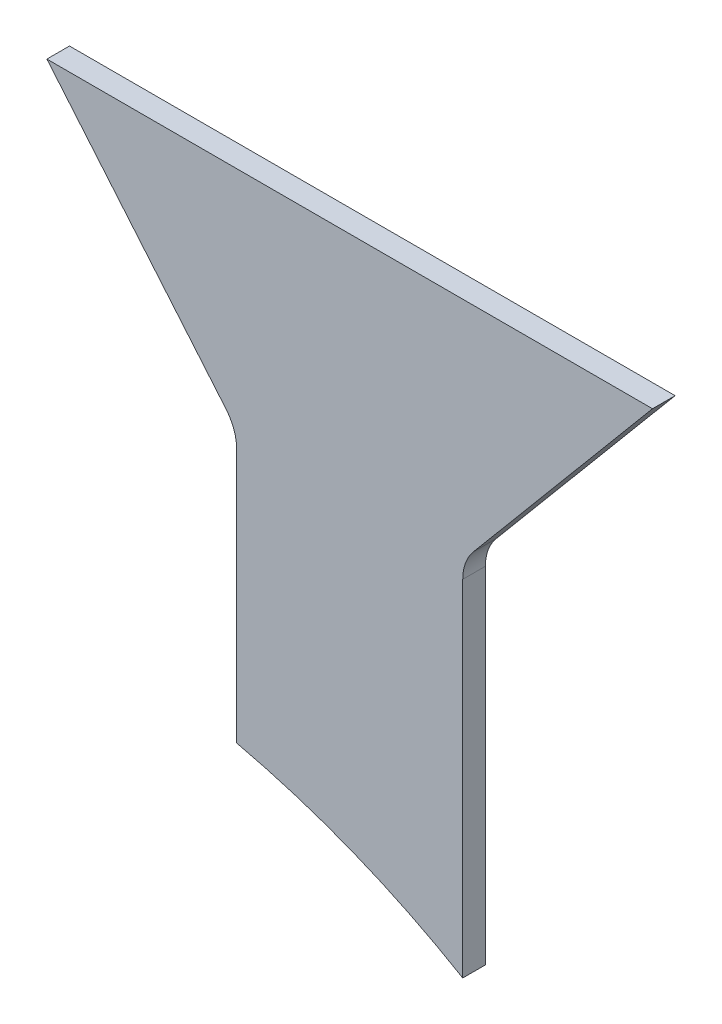
SolidWorks part; units mm, degrees
material "201 Annealed Stainless Steel (SS)"
ref_plane "Front Plane" through (0, 0, 0) normal (0, 0, 1) x (1, 0, 0)
ref_plane "Top Plane" through (0, 0, 0) normal (0, 1, 0) x (1, 0, 0)
ref_plane "Right Plane" through (0, 0, 0) normal (1, 0, 0) x (0, 0, -1)
sketch "Sketch1" plane through (0, 0, 0) normal (0, 0, 1) x (1, 0, 0)
  line L1 (25, 0) -> (25, 80)
  line L2 (25, 80) -> (66.974, 130.0227)
  line L6 (0, 0) -> (25, 0) construction
  line L7 (0, 0) -> (0, 130.0227) construction
  line L8 (-66.974, 130.0227) -> (66.974, 130.0227)
  line L9 (-25, 20) -> (-25, 80)
  line L10 (-25, 80) -> (-66.974, 130.0227)
  line L11 (0, 0) -> (0, -123.071) construction
  line L12 (-64.2195, -150.5486) -> (39.9259, -150.5486) construction
  line L13 (-25, 0) -> (-25, 20) construction
  line L14 (-25, 0) -> (0, 0) construction
  line L15 (-25, 20) -> (-25, -94.1356) construction
  line L16 (25, 0) -> (25, -97.0815) construction
  arc A1 (25, 0) -> (-25, 20) centre (-64.2195, -150.5486) ccw
  circle A2 centre (-64.2195, -150.5486) radius 175 construction
  point P4 (25, 0)
  point P16 (0, 0)
  dimension "D5" = 175
  dimension "D6" = 60
  dimension "D1" = 25
  dimension "D2" = 140
  dimension "D3" = 65.3
  dimension "D4" = 80
extrude "Funnel - Side Panel" add sketch "Sketch1" along normal blind 5
fillet "Fillet1" radius 10 2 edges at (-25, 80, 2.5) (25, 80, 2.5)
